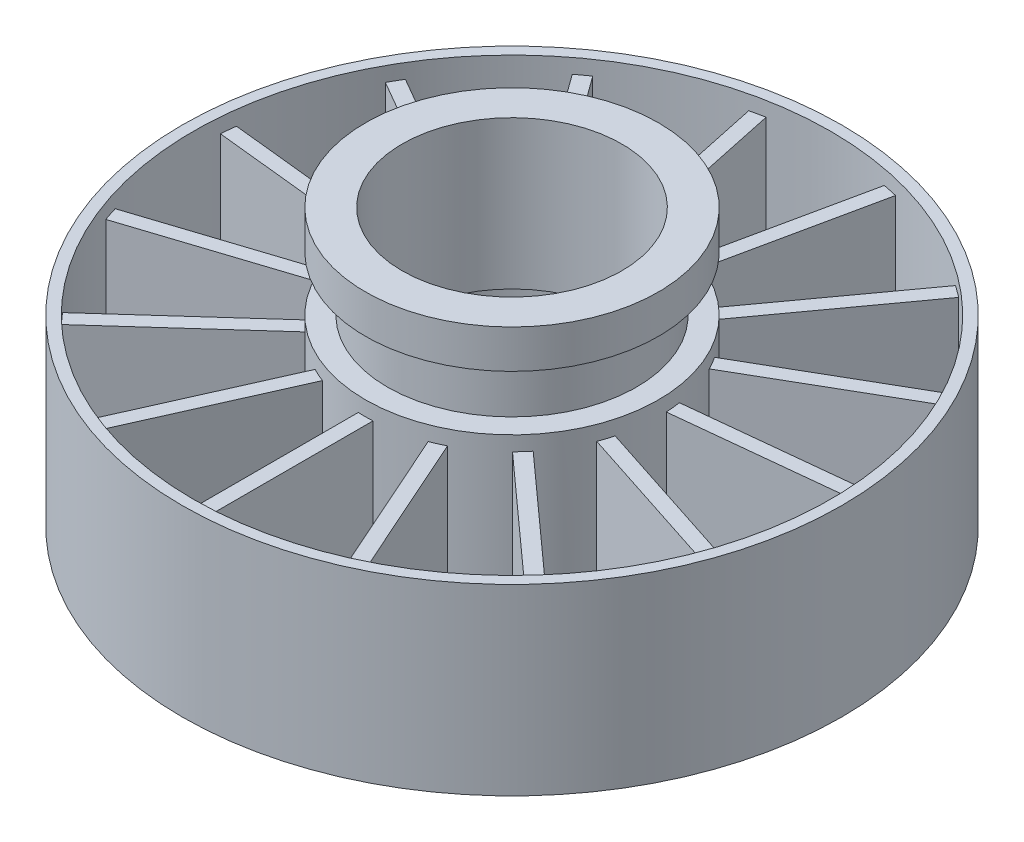
SolidWorks part; units mm, degrees
ref_plane "Front Plane" through (0, 0, 0) normal (0, 0, 1) x (1, 0, 0)
ref_plane "Top Plane" through (0, 0, 0) normal (0, 1, 0) x (1, 0, 0)
ref_plane "Right Plane" through (0, 0, 0) normal (1, 0, 0) x (0, 0, -1)
sketch "Sketch1" plane through (0, 0, 0) normal (0, 1, 0) x (1, 0, 0)
  circle A0 centre (0, 0) radius 90
  dimension "D1" = 180
extrude "Boss-Extrude1" add sketch "Sketch1" along normal blind 50
sketch "Sketch2" plane through (0, 0, 0) normal (0, -1, 0) x (1, 0, 0)
  line L0 (0, 90) -> (0, 0) construction
  line L1 (-2, 89.9778) -> (-2, 0)
  line L2 (-2, 0) -> (2, 0)
  line L3 (2, 0) -> (2, 89.9778)
  line L4 (34.7702, 83.0123) -> (-1.8271, 0.8135)
  line L5 (-1.8271, 0.8135) -> (1.8271, -0.8135)
  line L6 (1.8271, -0.8135) -> (38.4243, 81.3853)
  line L7 (36.6063, 82.2191) -> (0, 0) construction
  line L8 (65.5283, 61.6932) -> (-1.3383, 1.4863)
  line L9 (-1.3383, 1.4863) -> (1.3383, -1.4863)
  line L10 (1.3383, -1.4863) -> (68.2048, 58.7206)
  line L11 (66.883, 60.2218) -> (0, 0) construction
  line L12 (84.9559, 29.7068) -> (-0.618, 1.9021)
  line L13 (-0.618, 1.9021) -> (0.618, -1.9021)
  line L14 (0.618, -1.9021) -> (86.192, 25.9025)
  line L15 (85.5951, 27.8115) -> (0, 0) construction
  line L16 (89.6939, -7.4162) -> (0.2091, 1.989)
  line L17 (0.2091, 1.989) -> (-0.2091, -1.989)
  line L18 (-0.2091, -1.989) -> (89.2758, -11.3943)
  line L19 (89.507, -9.4076) -> (0, 0) construction
  line L20 (78.923, -43.2568) -> (1, 1.7321)
  line L21 (1, 1.7321) -> (-1, -1.7321)
  line L22 (-1, -1.7321) -> (76.923, -46.7209)
  line L23 (77.9423, -45) -> (0, 0) construction
  line L24 (54.5056, -71.618) -> (1.618, 1.1756)
  line L25 (1.618, 1.1756) -> (-1.618, -1.1756)
  line L26 (-1.618, -1.1756) -> (51.2696, -73.9691)
  line L27 (52.9007, -72.8115) -> (0, 0) construction
  line L28 (20.6637, -87.5957) -> (1.9563, 0.4158)
  line L29 (1.9563, 0.4158) -> (-1.9563, -0.4158)
  line L30 (-1.9563, -0.4158) -> (16.7511, -88.4274)
  line L31 (18.7121, -88.0333) -> (0, 0) construction
  line L32 (-16.7511, -88.4274) -> (1.9563, -0.4158)
  line L33 (1.9563, -0.4158) -> (-1.9563, 0.4158)
  line L34 (-1.9563, 0.4158) -> (-20.6637, -87.5957)
  line L35 (-18.7121, -88.0333) -> (0, 0) construction
  line L36 (-51.2696, -73.9691) -> (1.618, -1.1756)
  line L37 (1.618, -1.1756) -> (-1.618, 1.1756)
  line L38 (-1.618, 1.1756) -> (-54.5056, -71.618)
  line L39 (-52.9007, -72.8115) -> (0, 0) construction
  line L40 (-76.923, -46.7209) -> (1, -1.7321)
  line L41 (1, -1.7321) -> (-1, 1.7321)
  line L42 (-1, 1.7321) -> (-78.923, -43.2568)
  line L43 (-77.9423, -45) -> (0, 0) construction
  line L44 (-89.2758, -11.3943) -> (0.2091, -1.989)
  line L45 (0.2091, -1.989) -> (-0.2091, 1.989)
  line L46 (-0.2091, 1.989) -> (-89.6939, -7.4162)
  line L47 (-89.507, -9.4076) -> (0, 0) construction
  line L48 (-86.192, 25.9025) -> (-0.618, -1.9021)
  line L49 (-0.618, -1.9021) -> (0.618, 1.9021)
  line L50 (0.618, 1.9021) -> (-84.9559, 29.7068)
  line L51 (-85.5951, 27.8115) -> (0, 0) construction
  line L52 (-68.2048, 58.7206) -> (-1.3383, -1.4863)
  line L53 (-1.3383, -1.4863) -> (1.3383, 1.4863)
  line L54 (1.3383, 1.4863) -> (-65.5283, 61.6932)
  line L55 (-66.883, 60.2218) -> (0, 0) construction
  line L56 (-38.4243, 81.3853) -> (-1.8271, -0.8135)
  line L57 (-1.8271, -0.8135) -> (1.8271, 0.8135)
  line L58 (1.8271, 0.8135) -> (-34.7702, 83.0123)
  line L59 (-36.6063, 82.2191) -> (0, 0) construction
  circle A0 centre (0, 0) radius 90
  point P155 (0, 0)
  circle M2 centre (0, 0) radius 90
  dimension "D1" = 180
  dimension "D2" = 4
  dimension "D3" = 15
extrude "Cut-Extrude1" cut sketch "Sketch2" against normal blind 50 contours L48 L46 M2 | L52 L50 M2 | L56 L54 M2 | L58 L1 M2 | L4 L3 M2 | L8 L6 M2 | L12 L10 M2 | L16 L14 M2 | L20 L18 M2 | L24 L22 M2 | L28 L26 M2 | L32 L30 M2 | L36 L34 M2 | L40 L38 M2 | L44 L42 M2 region at (-13.0686, 0, 61.4828) region at (13.0686, 0, 61.4828) region at (-36.9461, 0, 50.8519) region at (36.9461, 0, 50.8519) region at (-54.4352, 0, 31.4282) region at (54.4352, 0, 31.4282) region at (-62.5121, 0, 6.5703) region at (62.5121, 0, 6.5703) region at (-59.78, 0, -19.4237) region at (59.78, 0, -19.4237) region at (-46.7114, 0, -42.0591) region at (46.7114, 0, -42.0591) region at (-25.566, 0, -57.4222) region at (25.566, 0, -57.4222) region at (0, 0, -62.8564)
sketch "Sketch4" plane through (0, 50, 0) normal (0, 1, 0) x (1, 0, 0)
  circle A0 centre (0, 0) radius 40
  dimension "D1" = 80
extrude "Cut-Extrude2" cut sketch "Sketch4" against normal through all
sketch "Sketch5" plane through (0, 50, 0) normal (0, 1, 0) x (1, 0, 0)
  circle A0 centre (0, 0) radius 40
  circle A1 centre (0, 0) radius 34
extrude "Boss-Extrude2" add sketch "Sketch5" against normal blind 50
sketch "Sketch9" plane through (0, 50, 0) normal (0, 1, 0) x (1, 0, 0)
  circle A0 centre (0, 0) radius 30
  circle A2 centre (0, 0) radius 34
  circle A4 centre (0, 0) radius 34 construction
  dimension "D1" = 60
extrude "Boss-Extrude3" add sketch "Sketch9" against normal blind 15 and the other way blind 15
sketch "Sketch10" plane through (0, 65, 0) normal (0, 1, 0) x (1, 0, 0)
  circle A0 centre (0, 0) radius 40
  circle A1 centre (0, 0) radius 30 construction
  circle A2 centre (0, 0) radius 30
extrude "Boss-Extrude4" add sketch "Sketch10" along normal blind 10.5
sketch "Sketch11" plane through (0, 0, 0) normal (0, -1, 0) x (1, 0, 0)
  circle A0 centre (0, 0) radius 90
  circle A1 centre (0, 0) radius 87
  dimension "D1" = 174
extrude "Boss-Extrude5" add sketch "Sketch11" against normal up to surface (50 mm away) up to face at (13.5105, 50, -63.5619)
sketch "Sketch12" plane through (0, 50, 0) normal (0, 1, 0) x (1, 0, 0)
  circle A0 centre (0, 0) radius 40
  circle A1 centre (0, 0) radius 87
extrude "Cut-Extrude3" cut sketch "Sketch12" against normal blind 4
sketch "Sketch13" plane through (0, 0, 0) normal (0, -1, 0) x (1, 0, 0)
  circle A0 centre (0, 0) radius 87
extrude "Cut-Extrude4" cut sketch "Sketch13" against normal blind 4
ref_plane "Plane1" through (0, 75.5, 0) normal (0, 1, 0) x (1, 0, 0)
sketch "Sketch14" plane through (0, 75.5, 0) normal (0, 1, 0) x (1, 0, 0)
  circle A0 centre (0, 0) radius 35
  point P3 (-35, 0)
  point P4 (0, 35)
  point P5 (35, 0)
  point P6 (0, -35)
